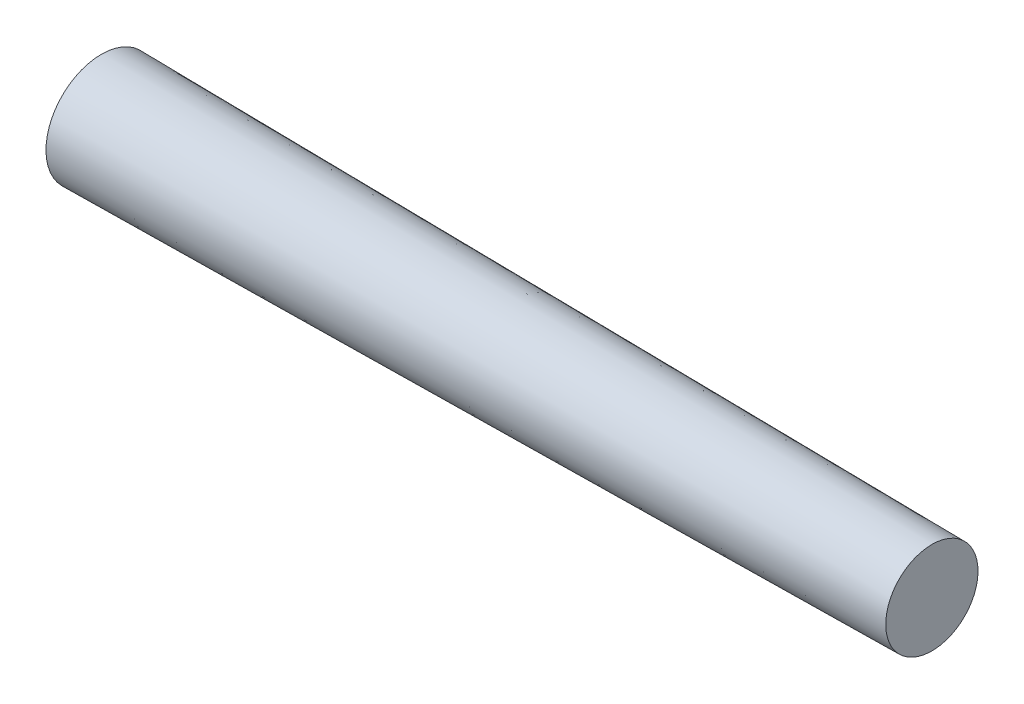
SolidWorks part; units mm, degrees
material "Plain Carbon Steel"
ref_plane "Front Plane" through (0, 0, 0) normal (0, 0, 1) x (1, 0, 0)
ref_plane "Top Plane" through (0, 0, 0) normal (0, 1, 0) x (1, 0, 0)
ref_plane "Right Plane" through (0, 0, 0) normal (1, 0, 0) x (0, 0, -1)
sketch "Sketch1" plane through (0, 0, 0) normal (0, 0, 1) x (1, 0, 0)
  line L0 (0, 0) -> (45, 0) construction
  line L1 (0, 0) -> (0, 3)
  line L2 (0, 3) -> (45, 2.5)
  line L3 (45, 2.5) -> (45, 0)
  line L4 (45, 0) -> (0, 0)
revolve "Revolve1" add sketch "Sketch1" angle 360 about L0
